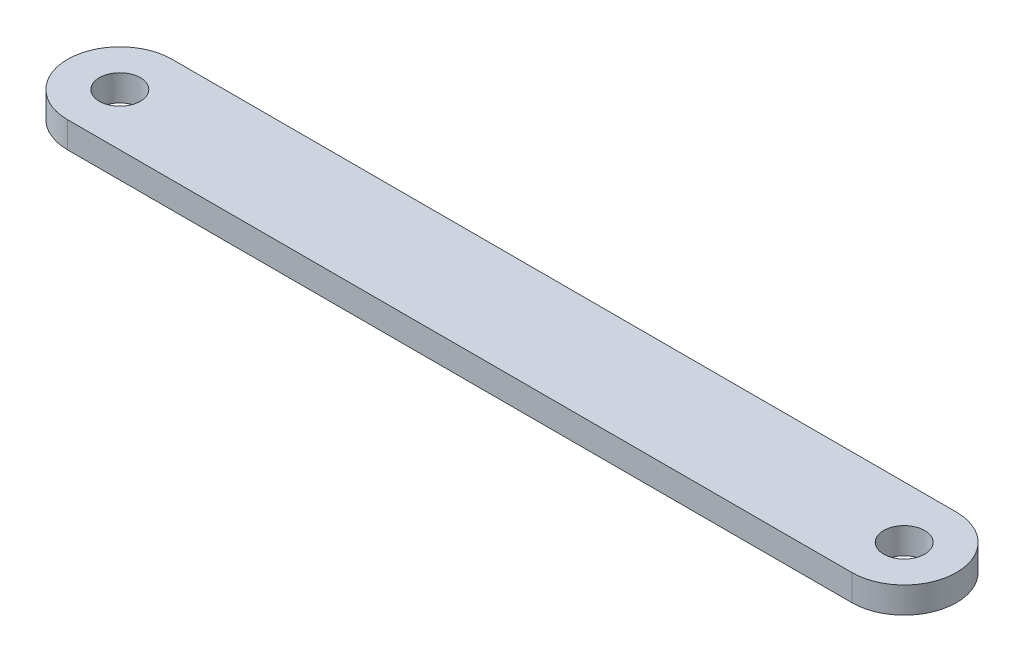
SolidWorks part; units mm, degrees
ref_plane "Front Plane" through (0, 0, 0) normal (0, 0, 1) x (1, 0, 0)
ref_plane "Top Plane" through (0, 0, 0) normal (0, 1, 0) x (1, 0, 0)
ref_plane "Right Plane" through (0, 0, 0) normal (1, 0, 0) x (0, 0, -1)
sketch "Sketch1" plane through (0, 0, 0) normal (0, 1, 0) x (1, 0, 0)
  line L0 (-47.625, 0) -> (47.625, 0) construction
  line L1 (-47.625, 6.35) -> (47.625, 6.35)
  line L2 (-47.625, -6.35) -> (47.625, -6.35)
  arc A0 (-47.625, 6.35) -> (-47.625, -6.35) centre (-47.625, 0) ccw
  arc A1 (47.625, -6.35) -> (47.625, 6.35) centre (47.625, 0) ccw
  point P3 (0, 0)
  dimension "D2" = 6.35
  dimension "D1" = 95.25
extrude "Boss-Extrude1" add sketch "Sketch1" along normal blind 3.175
hole_wizard "#10 Clearance Hole1" positions "Sketch2" profile "Sketch3" hole size "#10" standard "ANSI Inch" end condition through all
sketch "Sketch2" plane through (0, 3.175, 0) normal (0, 1, 0) x (1, 0, 0)
  point P0 (-47.625, 0)
  point P3 (47.625, 0)
sketch "Sketch3" plane through (-47.625, 3.175, 0) normal (1, 0, 0) x (0, 0, 1)
  line L0 (0, 0) -> (0, 3.175)
  line L1 (0, 3.175) -> (2.4892, 3.175)
  line L2 (2.4892, 3.175) -> (2.4892, 0)
  line L5 (2.4892, 0) -> (0, 0)
  line L11 (0, -6.35) -> (0, 107.95) construction
  dimension "Thru Hole Dia." = 4.9784
  dimension "Thru Hole Depth" = 3.175
